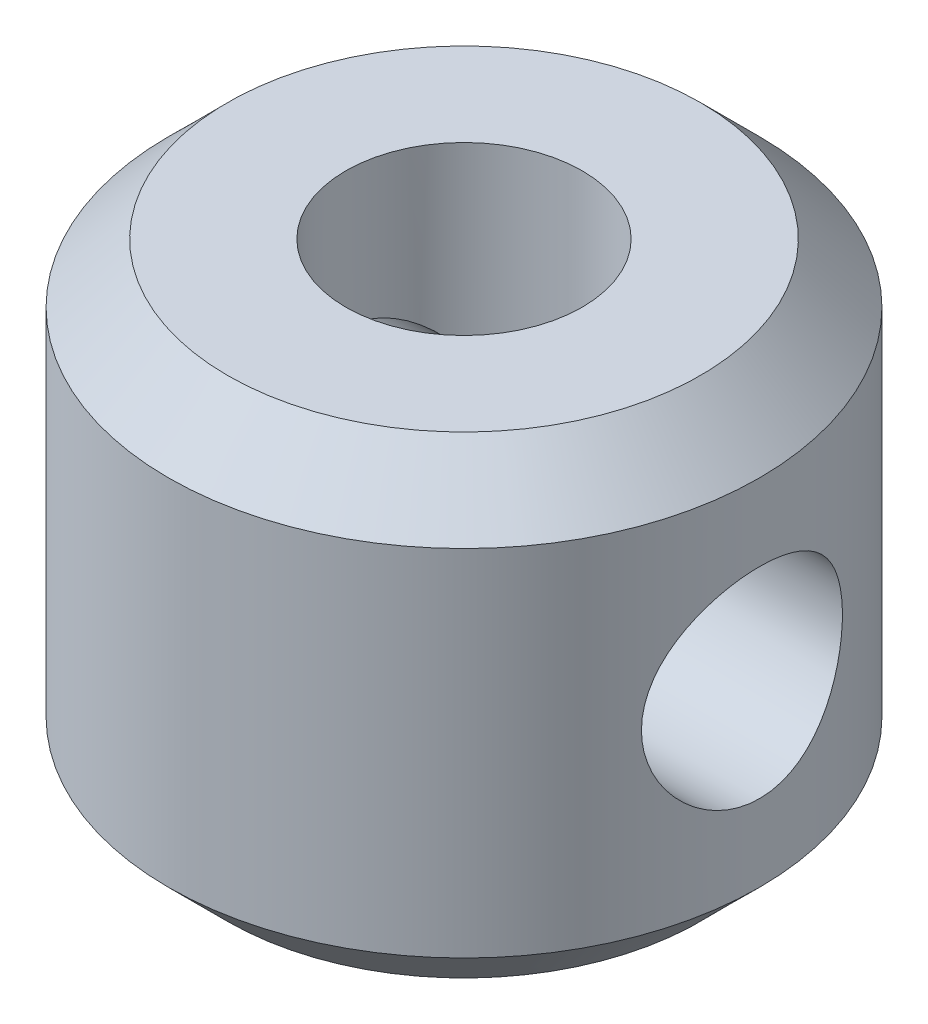
SolidWorks part; units mm, degrees
ref_plane "Front Plane" through (0, 0, 0) normal (0, 0, 1) x (1, 0, 0)
ref_plane "Top Plane" through (0, 0, 0) normal (0, 1, 0) x (1, 0, 0)
ref_plane "Right Plane" through (0, 0, 0) normal (1, 0, 0) x (0, 0, -1)
sketch "Sketch2" plane through (0, 0, 0) normal (0, 1, 0) x (1, 0, 0)
  circle A0 centre (0, 0) radius 4
  circle A1 centre (0, 0) radius 10
  dimension "D1" = 20
  dimension "D2" = 8
extrude "Boss-Extrude1" add sketch "Sketch2" along normal blind 8 and the other way blind 8
sketch "Sketch3" plane through (0, 0, 0) normal (1, 0, 0) x (0, 0, -1)
  circle A0 centre (0, 0) radius 3.4
  dimension "D1" = 6.8
extrude "Cut-Extrude1" cut sketch "Sketch3" against normal blind 20 and the other way blind 20
chamfer "Chamfer1" distance 2 angle 45 2 edges at (0, -8, 10) (0, 8, 10)
